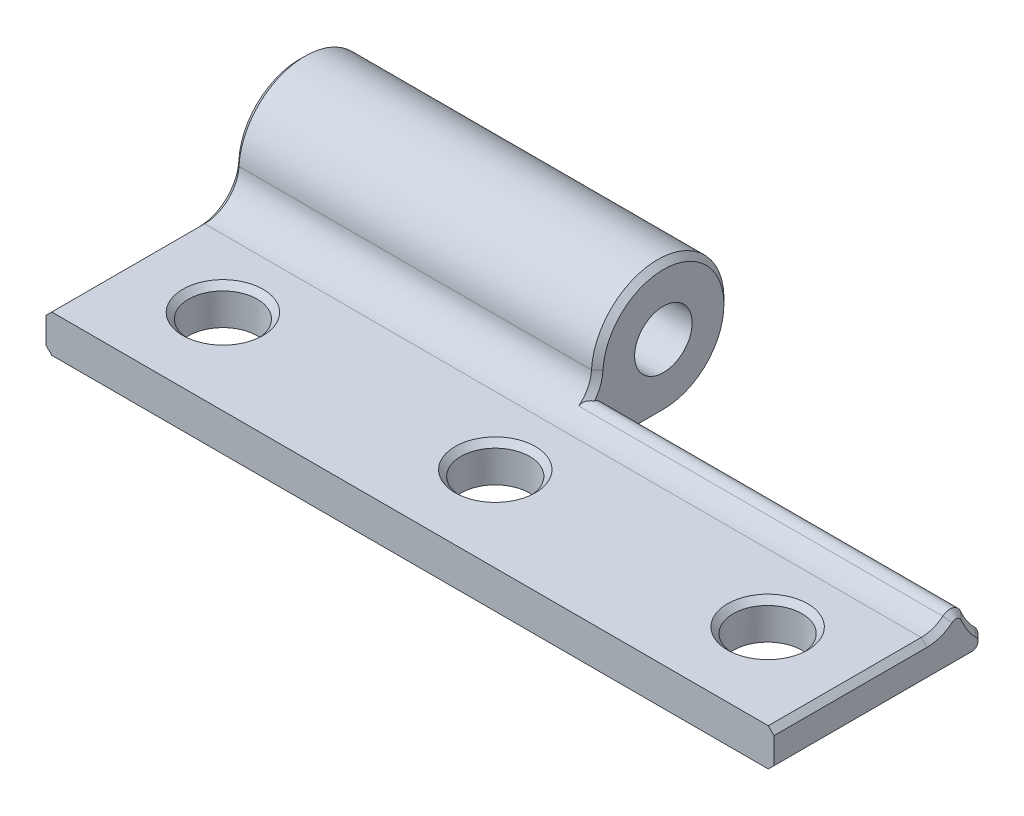
SolidWorks part; units mm, degrees
ref_plane "Front Plane" through (0, 0, 0) normal (0, 0, 1) x (1, 0, 0)
ref_plane "Top Plane" through (0, 0, 0) normal (0, 1, 0) x (1, 0, 0)
ref_plane "Right Plane" through (0, 0, 0) normal (1, 0, 0) x (0, 0, -1)
sketch "Sketch1" plane through (0, 0, 0) normal (1, 0, 0) x (0, 0, -1)
  line L0 (0, -5.7795) -> (-22.098, -5.7795)
  line L1 (-22.098, -5.7795) -> (-22.098, -2.509)
  line L2 (-22.098, -2.509) -> (-8.7658, -2.509)
  line L3 (0, -2.509) -> (-5.2065, -2.509) construction
  line L4 (-22.098, -13.2199) -> (22.098, -13.2199) construction
  line L5 (0, 0) -> (0, -13.2199) construction
  line L6 (-22.098, -5.7795) -> (-22.098, -13.2199) construction
  arc A0 (0, -5.7795) -> (-5.7705, 0.3232) centre (0, 0) ccw
  circle A1 centre (0, 0) radius 2.509
  arc A2 (-8.7658, -2.509) -> (-5.7705, 0.3232) centre (-8.7658, 0.491) ccw
  dimension "D1" = 3
  dimension "D2" = 44.196
extrude "Boss-Extrude1" add sketch "Sketch1" along normal mid plane 63.5
sketch "Sketch2" plane through (0, 0, 0) normal (1, 0, 0) x (0, 0, -1)
  circle A0 centre (0, 0) radius 5.7795
  arc A1 (0, -5.7795) -> (-5.7705, 0.3232) centre (0, 0) ccw construction
extrude "Cut-Extrude1" cut sketch "Sketch2" along normal blind 63.5
fillet "Fillet1" radius 1 2 edges at (15.875, -5.7795, 0) (15.875, 0.3232, 5.7705)
sketch "Sketch3" plane through (0, -2.509, 0) normal (0, 1, 0) x (1, 0, 0)
  line L0 (-23.7558, -14.6625) -> (23.7558, -14.6625) construction
  line L1 (0, 0) -> (0, -14.6625) construction
  circle A0 centre (-23.7558, -14.6625) radius 3
  circle A1 centre (0, -14.6625) radius 3
  circle A2 centre (23.7558, -14.6625) radius 3
  point P8 (-23.7558, -15.0856)
  dimension "D1" = 6
extrude "Cut-Extrude2" cut sketch "Sketch3" against normal through all
chamfer "Chamfer1" distance 0.5 angle 45 16 edges at (31.75, -5.7795, 13.4531) (31.75, -5.1636, 3.8848) (31.75, -3.2139, 4.8035) (31.75, -1.6512, 6.0078) (31.75, -2.3376, 7.7662) (31.75, -2.509, 15.4319) (-31.75, -2.509, 15.4319) (-31.75, -5.7795, 11.049) (-31.75, -1.6889, 6.7046) (-31.75, 3.9708, -4.1995) (0, -5.7795, 2.4041) (0, -0.8775, 6.0961) (0, 3.9708, -4.1995) (23.7558, -2.509, 17.6625) (0, -2.509, 17.6625) (-23.7558, -2.509, 17.6625)
